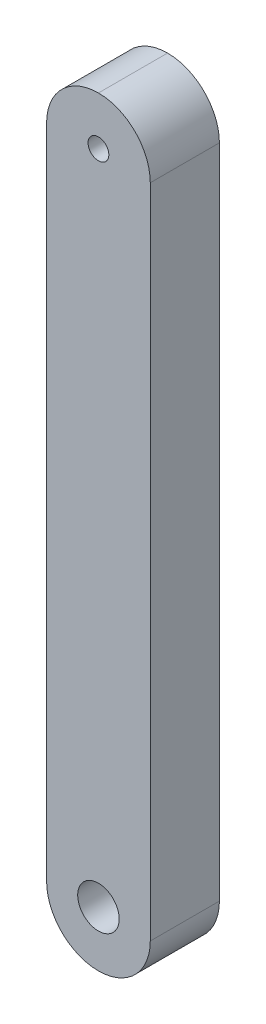
SolidWorks part; units mm, degrees
ref_plane "Front" through (0, 0, 0) normal (0, 0, 1) x (1, 0, 0)
ref_plane "Top" through (0, 0, 0) normal (0, 1, 0) x (1, 0, 0)
ref_plane "Right" through (0, 0, 0) normal (1, 0, 0) x (0, 0, -1)
sketch "Esquisse1" plane through (0, 0, 0) normal (0, 0, 1) x (1, 0, 0)
  line L1 (0, 0) -> (15, 0)
  line L2 (0, 0) -> (0, 110)
  line L3 (0, 110) -> (15, 110)
  line L4 (15, 0) -> (15, 110)
  dimension "D1" = 15
  dimension "D2" = 110
extrude "Boss.-Extru.1" add sketch "Esquisse1" along normal blind 10
sketch "Esquisse2" plane through (0, 0, 10) normal (0, 0, 1) x (1, 0, 0)
  line L0 (7.5, 103) -> (7.5, 110) construction
  line L1 (15, 110) -> (0, 110) construction
  line L2 (0, 0) -> (15, 0) construction
  line L3 (7.5, 8) -> (7.5, 0) construction
  circle A1 centre (7.5, 103) radius 1.5
  circle A2 centre (7.5, 8) radius 3
  point P11 (7.5, 0)
  dimension "D2" = 7
  dimension "D3" = 3
  dimension "D4" = 6
  dimension "D5" = 8
extrude "Enlèv. mat.-Extru.1" cut sketch "Esquisse2" against normal up to vertex (10 mm away) up to point (0, 110, 0)
fillet "Congé1" radius 7.5 4 edges at (15, 110, 5) (0, 110, 5) (15, 0, 5) (0, 0, 5)
